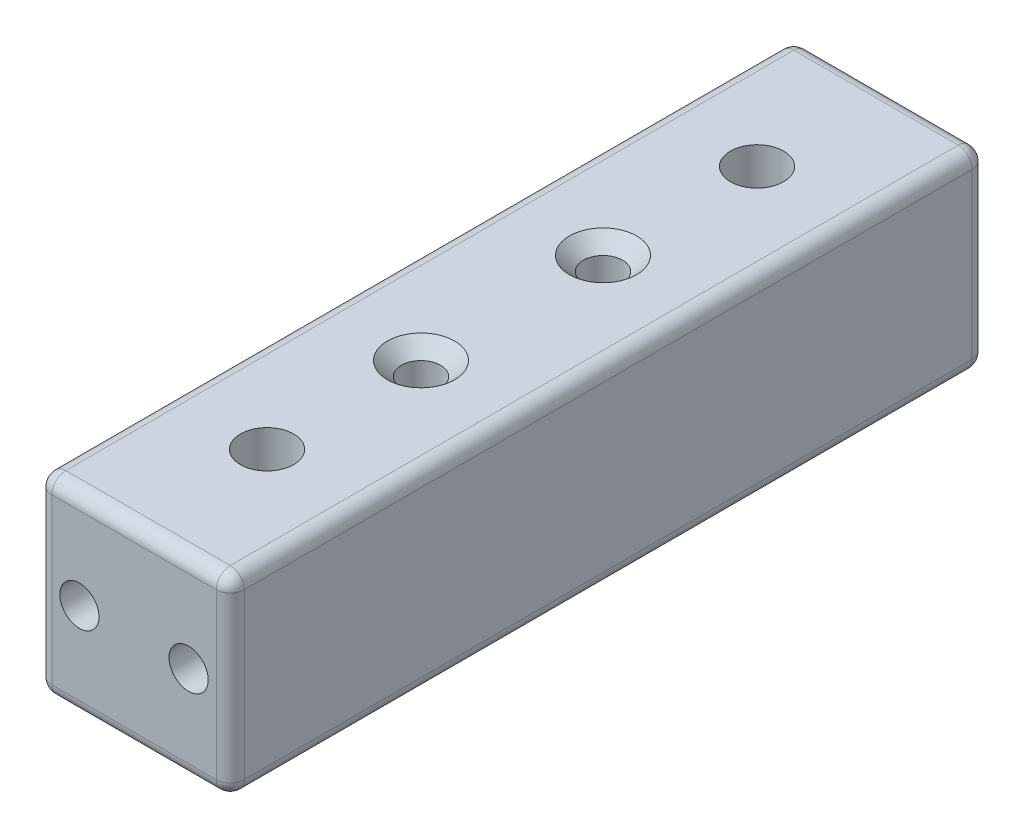
SolidWorks part; units mm, degrees
ref_plane "Front Plane" through (0, 0, 0) normal (0, 0, 1) x (1, 0, 0)
ref_plane "Top Plane" through (0, 0, 0) normal (0, 1, 0) x (1, 0, 0)
ref_plane "Right Plane" through (0, 0, 0) normal (1, 0, 0) x (0, 0, -1)
sketch "Sketch1" plane through (0, 0, 0) normal (0, 0, 1) x (1, 0, 0)
  line L1 (-6.875, -6.875) -> (6.875, -6.875)
  line L2 (-6.875, -6.875) -> (-6.875, 6.875)
  line L3 (-6.875, 6.875) -> (6.875, 6.875)
  line L4 (6.875, -6.875) -> (6.875, 6.875)
  line L5 (-6.875, -6.875) -> (6.875, 6.875) construction
  line L6 (-6.875, 6.875) -> (6.875, -6.875) construction
  point P0 (0, 0)
  dimension "D1" = 13.75
extrude "Boss-Extrude1" add sketch "Sketch1" along normal blind 54
ref_axis "Axis1" through (0, 0, -0.8) along (0, 0, 1)
sketch "Sketch3" plane through (0, 6.875, 0) normal (0, 1, 0) x (1, 0, 0)
  line L0 (0, -9.5) -> (0, 0) construction
  line L1 (6.875, 0) -> (-6.875, 0) construction
  line L2 (0, -9.5) -> (0, -44.5) construction
  circle A0 centre (0, -9.5) radius 6.5 construction
  circle A1 centre (0, -9.5) radius 1.9
  circle A2 centre (0, -44.5) radius 1.9
  circle A3 centre (0, -20.5) radius 1.4
  circle A4 centre (0, -33.5) radius 1.4
  dimension "D1" = 13
  dimension "D3" = 3.8
  dimension "D4" = 35
  dimension "D6" = 2.8
  dimension "D2" = 3
  dimension "D5" = 9.5
  dimension "D7" = 11
  dimension "D8" = 11
extrude "Cut-Extrude2" cut sketch "Sketch3" against normal through all
sketch "Sketch9" plane through (0, 0, 0) normal (0, 0, -1) x (-1, 0, 0)
  line L0 (-3.9, 0) -> (0, 0) construction
  line L1 (-2, 1.1669) -> (-2, -1.0479) construction
  line L2 (0, 0.6668) -> (0, -0.643) construction
  circle A0 centre (-3.9, 0) radius 1.4
  dimension "D1" = 2.8
  dimension "D3" = 0.5
  dimension "D2" = 4
extrude "Cut-Extrude7" cut sketch "Sketch9" against normal through all
mirror "Mirror5" about plane through (0, 0, 0) normal (1, 0, 0) of "Cut-Extrude7"
fillet "Fillet2" radius 1 12 edges at (0, 6.875, 0) (-6.875, 0, 0) (0, -6.875, 0) (6.875, 0, 0) (6.875, 0, 54) (-6.875, 0, 54) (0, 6.875, 54) (6.875, -6.875, 27) (-6.875, -6.875, 27) (6.875, 6.875, 27) (-6.875, 6.875, 27) (0, -6.875, 54)
chamfer "Chamfer1" distance 1 angle 45 4 edges at (0, -6.875, 21.9) (0, -6.875, 34.9) (0, 6.875, 34.9) (0, 6.875, 21.9)
